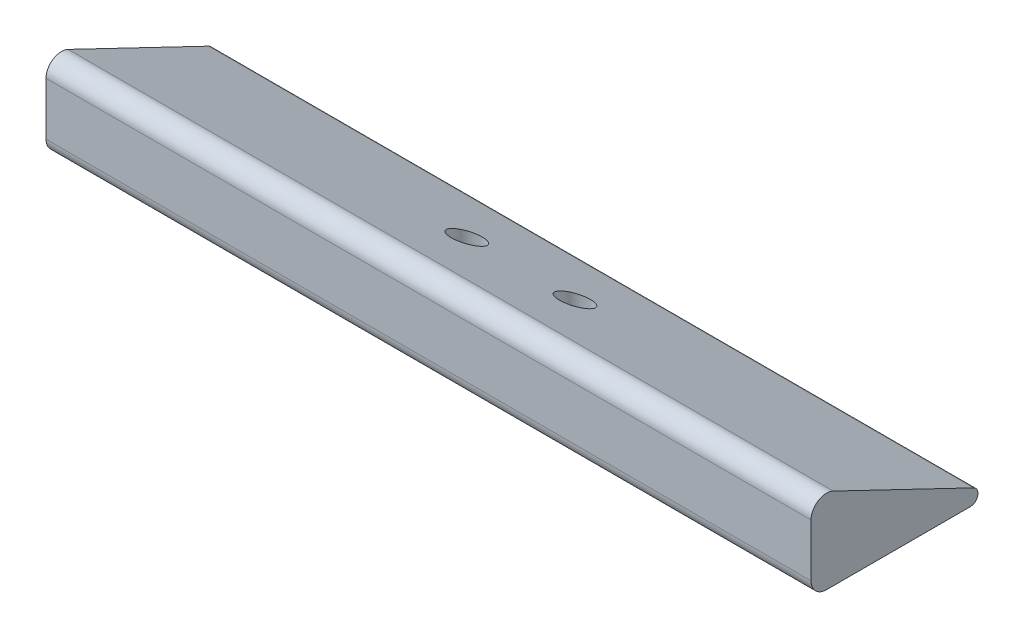
SolidWorks part; units mm, degrees
material "Rubber"
ref_plane "Front Plane" through (0, 0, 0) normal (0, 0, 1) x (1, 0, 0)
ref_plane "Top Plane" through (0, 0, 0) normal (0, 1, 0) x (1, 0, 0)
ref_plane "Right Plane" through (0, 0, 0) normal (1, 0, 0) x (0, 0, -1)
sketch "Sketch1" plane through (0, 0, 0) normal (1, 0, 0) x (0, 0, -1)
  line L0 (2, 0) -> (20.6058, 0)
  line L1 (21.0385, 1.9015) -> (2.8655, 10.6246)
  line L2 (0, 8.8215) -> (0, 2)
  arc A0 (0, 8.8215) -> (2.8655, 10.6246) centre (2, 8.8215) cw
  arc A1 (2, 0) -> (0, 2) centre (2, 2) cw
  arc A2 (21.0385, 1.9015) -> (20.6058, 0) centre (20.6058, 1) cw
  point P6 (0, 12)
  point P9 (0, 0)
  point P12 (25, 0)
  dimension "D1" = 12
  dimension "D3" = 2
  dimension "D4" = 1
  dimension "D2" = 25
extrude "Boss-Extrude1" add sketch "Sketch1" along normal blind 99
ref_plane "Plane1" through (0, 10, 0) normal (0, 1, 0) x (1, 0, 0)
sketch "Sketch2" plane through (0, 10, 0) normal (0, 1, 0) x (1, 0, 0)
  line L0 (99, 11.952) -> (0, 11.952) construction
  line L1 (99, 21.0385) -> (99, 2.8655) construction
  line L2 (0, 21.0385) -> (0, 2.8655) construction
  line L3 (49.5, 11.952) -> (49.5, 18.9766) construction
  circle A0 centre (42.5, 11.952) radius 2
  circle A1 centre (56.5, 11.952) radius 2
  dimension "D1" = 4
  dimension "D2" = 7
extrude "Cut-Extrude1" cut sketch "Sketch2" against normal blind 8
sketch "Sketch3" plane through (0, 2, 0) normal (0, 1, 0) x (1, 0, 0)
  circle A0 centre (42.5, 11.952) radius 1.5
  circle A1 centre (56.5, 11.952) radius 1.5
  dimension "D1" = 3
extrude "Cut-Extrude2" cut sketch "Sketch3" against normal through all
sketch "Sketch4" [suppressed] plane through (0, 0, 0) normal (1, 0, 0) x (0, 0, -1)
  line L0 (0, 1) -> (0, 10.4108)
  line L1 (1.4327, 11.3123) -> (21.0385, 1.9015)
  line L2 (20.6058, 0) -> (1, 0)
  arc A0 (20.6058, 0) -> (21.0385, 1.9015) centre (20.6058, 1) ccw
  arc A1 (1, 0) -> (0, 1) centre (1, 1) cw
  arc A2 (1.4327, 11.3123) -> (0, 10.4108) centre (1, 10.4108) ccw
  point P6 (25, 0)
  point P9 (0, 0)
  point P12 (0, 12)
  dimension "D3" = 1
  dimension "D1" = 25
  dimension "D2" = 12
extrude "Boss-Extrude2" [suppressed] add sketch "Sketch4" along normal blind 40
ref_plane "Plane2" [suppressed] through (0, 10, 0) normal (0, -1, 0) x (-1, 0, 0)
sketch "Sketch5" [suppressed] plane through (0, 10, 0) normal (0, -1, 0) x (-1, 0, 0)
  line L0 (-15, 0) -> (-15, 21.6058) construction
  line L1 (-30, 0) -> (0, 0) construction
  line L2 (0, 21.6058) -> (-30, 21.6058) construction
  line L3 (-15, 10.8029) -> (-8, 10.8029) construction
  circle A0 centre (-8, 10.8029) radius 2
  circle A1 centre (-22, 10.8029) radius 2
  dimension "D1" = 4
  dimension "D2" = 14
extrude "Cut-Extrude4" [suppressed] cut sketch "Sketch5" along normal blind 8
sketch "Sketch6" [suppressed] plane through (0, 2, 0) normal (0, 1, 0) x (1, 0, 0)
  circle A0 centre (8, 10.8029) radius 1.5
  circle A1 centre (22, 10.8029) radius 1.5
  dimension "D1" = 3
extrude "Cut-Extrude5" [suppressed] cut sketch "Sketch6" against normal blind 8
